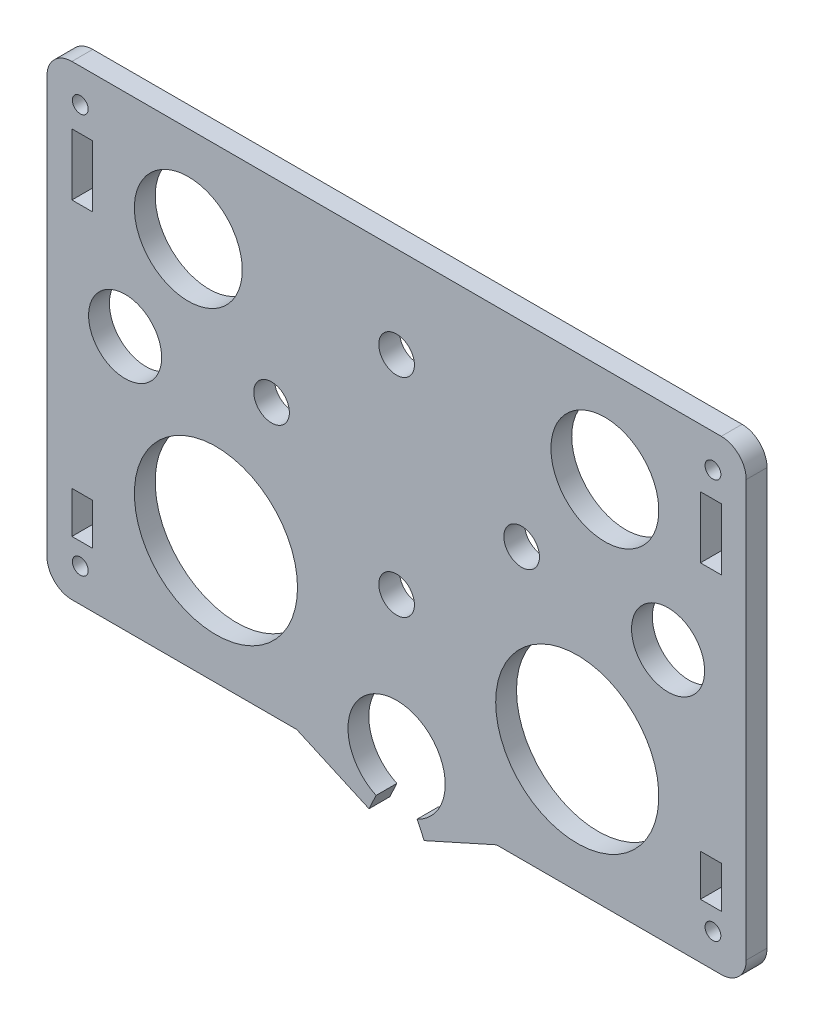
SolidWorks part; units mm, degrees
material "Delrin 2700 NC010, Low Viscosity Acetal Copolymer (SS)"
ref_plane "Front Plane" through (0, 0, 0) normal (0, 0, 1) x (1, 0, 0)
ref_plane "Top Plane" through (0, 0, 0) normal (0, 1, 0) x (1, 0, 0)
ref_plane "Right Plane" through (0, 0, 0) normal (1, 0, 0) x (0, 0, -1)
sketch "Sketch1" plane through (0, 0, 0) normal (0, 0, 1) x (1, 0, 0)
  line L0 (0, -1000) -> (0, 49000) construction
  line L1 (24.765, 17.78) -> (-24.765, 17.78)
  line L2 (26.67, 15.875) -> (26.67, -17.78)
  line L3 (26.67, -17.78) -> (-26.67, -17.78)
  line L4 (-26.67, 15.875) -> (-26.67, -17.78)
  line L5 (26.67, 17.78) -> (-26.67, -17.78) construction
  line L6 (26.67, -17.78) -> (-26.67, 17.78) construction
  line L7 (-1000, 0) -> (49000, 0) construction
  line L8 (-7.62, -17.78) -> (-2.104, -20.26)
  line L15 (-2.104, -20.26) -> (0, -15.748)
  line L16 (7.62, -17.78) -> (2.104, -20.26)
  line L17 (2.104, -20.26) -> (0, -15.748)
  line L18 (0, 0) -> (-24.2469, 20.3456) construction
  circle A0 centre (0, -15.748) radius 3.7084
  circle A1 centre (-24.13, 15.24) radius 0.6032
  circle A3 centre (24.13, 15.24) radius 0.6033
  arc A7 (24.765, -17.78) -> (26.67, -15.875) centre (24.765, -15.875) ccw
  arc A8 (-24.765, -17.78) -> (-26.67, -15.875) centre (-24.765, -15.875) cw
  arc A9 (-24.765, 17.78) -> (-26.67, 15.875) centre (-24.765, 15.875) ccw
  arc A10 (24.765, 17.78) -> (26.67, 15.875) centre (24.765, 15.875) cw
  circle A11 centre (24.13, -15.24) radius 0.6033
  circle A12 centre (-24.13, -15.24) radius 0.6032
  circle A13 centre (0, -15.748) radius 4.9784
  point P0 (0, 0)
  point P9 (0, 0)
  point P11 (0, -7.366)
  point P53 (-13.97, 0)
  dimension "D6" = 7.4168
  dimension "D7" = 1.2065
  dimension "D14" = 1.905
  dimension "D15" = 1.905
  dimension "D30" = 2.54
  dimension "D1" = 35.56
  dimension "D4" = 53.34
  dimension "D5" = 15.748
  dimension "D8" = 2.54
  dimension "D19" = 40
  dimension "D20" = 8.382
  dimension "D23" = 13.97
  dimension "D27" = 7.62
  dimension "D28" = 25
  dimension "D26" = 1.27
extrude "Boss-Extrude1" add sketch "Sketch1" along normal blind 1.5875 contours A10 L1 A9 L4 L3 A0 L2 A1 A3 | L3 A13 L15 A0 | A13 L3 L8 | L3 A13 A0 | L17 A13 L3 A0 | A13 L16 L3 region at (0, 0.4698, 0) region at (5.0756, -18.4873, 0) region at (-5.0756, -18.4873, 0) region at (2.9865, -18.87, 0) region at (3.8235, -17.6582, 0) region at (-2.9865, -18.87, 0)
ref_axis "Axis1" through (0, 0, 0) along (0, 0, 1)
sketch "Sketch5" plane through (0, 0, 1.5875) normal (0, 0, 1) x (1, 0, 0)
  line L0 (24.765, 8.6264) -> (23.1775, 8.6264) construction
  line L1 (24.765, -10.4236) -> (23.1775, -10.4236) construction
  line L2 (24.765, -10.4236) -> (23.1775, -10.4236)
  line L3 (23.1775, -10.4236) -> (23.1775, -13.5986)
  line L4 (24.765, 8.6264) -> (23.1775, 8.6264)
  line L5 (23.1775, -13.5986) -> (24.765, -13.5986)
  line L6 (24.765, -13.5986) -> (24.765, -10.4236)
  line L8 (24.765, 8.6264) -> (24.765, 13.3254)
  line L9 (24.765, 13.3254) -> (23.1775, 13.3254)
  line L10 (23.1775, 13.3254) -> (23.1775, 8.6264)
  dimension "D1" = 4.699
  dimension "D2" = 3.175
extrude "Cut-Extrude1" cut sketch "Sketch5" against normal through all
mirror "Mirror1" about plane through (0, 0, 0) normal (1, 0, 0) of "Cut-Extrude1"
sketch "Sketch6" plane through (0, 0, 1.5875) normal (0, 0, 1) x (1, 0, 0)
  line L0 (0, -12.0396) -> (0, 17.78) construction
  line L1 (24.765, 17.78) -> (-24.765, 17.78) construction
  arc A0 (1.5672, -19.109) -> (-1.5672, -19.109) centre (0, -15.748) ccw construction
  point P7 (0, 2.8702)
  point P8 (-21.055, 25.8958)
sketch "Sketch7" plane through (0, 0, 1.5875) normal (0, 0, 1) x (1, 0, 0)
  circle A0 centre (0, 10.795) radius 1.3589 construction
  circle A1 centre (9.5377, 2.8702) radius 1.3589 construction
  circle A2 centre (-9.5377, 2.8702) radius 1.3589 construction
  circle A3 centre (0, -5.0546) radius 1.3589 construction
  circle A4 centre (0, 10.795) radius 1.3589
  circle A5 centre (9.5377, 2.8702) radius 1.3589
  circle A6 centre (-9.5377, 2.8702) radius 1.3589
  circle A7 centre (0, -5.0546) radius 1.3589
extrude "Cut-Extrude2" cut sketch "Sketch7" against normal through all
sketch "Sketch8" plane through (0, 0, 1.5875) normal (0, 0, 1) x (1, 0, 0)
  line L0 (-15.8876, 14.605) -> (11.3838, 14.605) construction
  line L1 (-20.0025, 10.4901) -> (-20.0025, 4.9728) construction
  line L2 (24.765, 17.78) -> (-24.765, 17.78) construction
  line L3 (-23.1775, 13.3254) -> (-23.1775, 8.6264) construction
  line L4 (-20.0025, -8.3828) -> (-20.0025, -26.6334) construction
  line L5 (-13.7803, -14.605) -> (2.6191, -14.605) construction
  line L6 (-23.1775, -10.4236) -> (-23.1775, -13.5986) construction
  line L7 (10.8966, 2.8702) -> (-51.4878, 2.8702) construction
  line L8 (-7.62, -17.78) -> (-24.765, -17.78) construction
  line L9 (-13.2533, 7.3289) -> (-15.8876, 10.4901) construction
  line L10 (-10.4076, 3.9141) -> (-9.5377, 2.8702) construction
  line L11 (-13.7803, -8.3828) -> (-11.5852, -2.5606) construction
  line L12 (-13.2533, 7.3289) -> (-10.4076, 3.9141) construction
  line L13 (-11.5852, -2.5606) -> (-10.0171, 1.5987) construction
  line L14 (-10.0171, 1.5987) -> (-9.5377, 2.8702) construction
  line L15 (0, -12.0396) -> (0, 17.78) construction
  circle A0 centre (9.5377, 2.8702) radius 1.3589 construction
  circle A1 centre (13.7803, -8.3828) radius 6.2222
  circle A2 centre (-15.8876, 10.4901) radius 4.1149
  circle A3 centre (-13.7803, -8.3828) radius 6.2222
  circle A4 centre (-9.5377, 2.8702) radius 1.3589 construction
  circle A5 centre (15.8876, 10.4901) radius 4.1149
  dimension "D1" = 3.175
  dimension "D2" = 3.175
  dimension "D3" = 3.175
  dimension "D4" = 3.175
  dimension "D5" = 4.445
extrude "Cut-Extrude3" cut sketch "Sketch8" against normal through all
sketch "Sketch9" plane through (0, 0, 1.5875) normal (0, 0, 1) x (1, 0, 0)
  line L0 (-23.495, 1.6406) -> (-23.495, 7.656) construction
  line L2 (-15.8876, 10.4901) -> (-17.8559, 6.8764) construction
  line L3 (-17.8559, 6.8764) -> (-19.3746, 4.0882) construction
  line L4 (-19.3746, 4.0882) -> (-20.7078, 1.6406) construction
  line L5 (-20.7078, 1.6406) -> (-19.1232, -0.6522) construction
  line L6 (-19.1232, -0.6522) -> (-17.318, -3.2641) construction
  line L7 (-17.318, -3.2641) -> (-13.7803, -8.3828) construction
  line L8 (-26.67, 15.875) -> (-26.67, -15.875) construction
  line L9 (0, 17.78) -> (0, -33.4642) construction
  circle A0 centre (-20.7078, 1.6406) radius 2.7872
  circle A1 centre (-15.8876, 10.4901) radius 4.1149 construction
  circle A2 centre (-13.7803, -8.3828) radius 6.2222 construction
  circle A3 centre (20.7078, 1.6406) radius 2.7872
  dimension "D1" = 3.175
  dimension "D2" = 3.175
extrude "Cut-Extrude4" cut sketch "Sketch9" against normal through all
